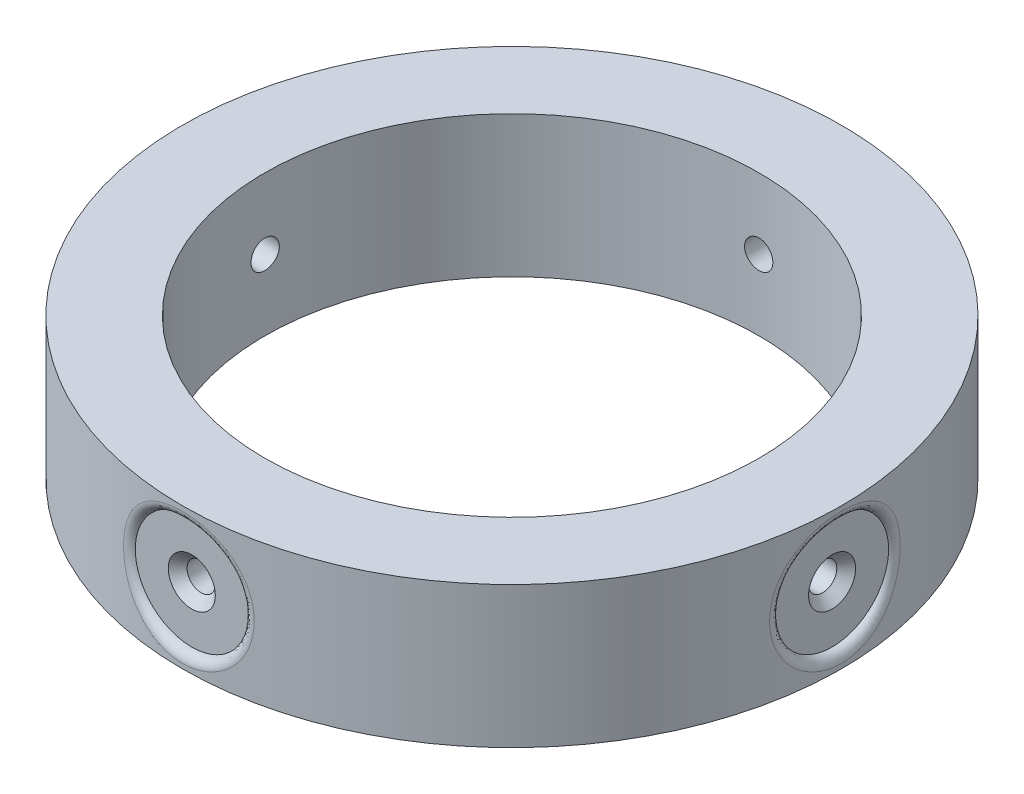
SolidWorks part; units mm, degrees
ref_plane "Front Plane" through (0, 0, 0) normal (0, 0, 1) x (1, 0, 0)
ref_plane "Top Plane" through (0, 0, 0) normal (0, 1, 0) x (1, 0, 0)
ref_plane "Right Plane" through (0, 0, 0) normal (1, 0, 0) x (0, 0, -1)
sketch "Sketch1" plane through (0, 0, 0) normal (0, 1, 0) x (1, 0, 0)
  circle A0 centre (0, 0) radius 26.25
  circle A1 centre (0, 0) radius 35
  dimension "D1" = 52.5
  dimension "D2" = 70
extrude "Boss-Extrude1" add sketch "Sketch1" along normal blind 15
ref_plane "Plane1" through (0, 0, 35) normal (0, 0, 1) x (1, 0, 0)
sketch "Sketch2" plane through (0, 0, 35) normal (0, 0, 1) x (1, 0, 0)
  line L0 (0, 15) -> (0, 0) construction
  line L1 (35, 15) -> (-35, 15) construction
  line L2 (-35, 7.5) -> (35, 7.5) construction
  line L3 (-35, 15) -> (-35, 0) construction
  line L4 (35, 0) -> (35, 15) construction
  circle A0 centre (0, 7.5) radius 6
  circle A1 centre (0, 7.5) radius 1.5
  dimension "D1" = 12
  dimension "D2" = 3
extrude "Cut-Extrude1" cut sketch "Sketch2" against normal blind 15 contours A1 region at (0, 7.5, 35)
extrude "Cut-Extrude2" cut sketch "Sketch2<3>" against normal blind 1
sketch "Sketch2<3>" plane through (0, 0, 35) normal (0, 0, 1) x (1, 0, 0) same geometry as "Sketch2"
fillet "Fillet1" radius 1 1 edges at (-5.8615, 8.7819, 34.5057)
chamfer "Chamfer1" distance 1 angle 45 1 edges at (1.5, 7.5, 34)
pattern_circular "CirPattern1" count 4 over 360 about axis through (0, 15, 0) along (0, 1, 0) of "Cut-Extrude2", "Cut-Extrude1", "Fillet1", "Chamfer1"
